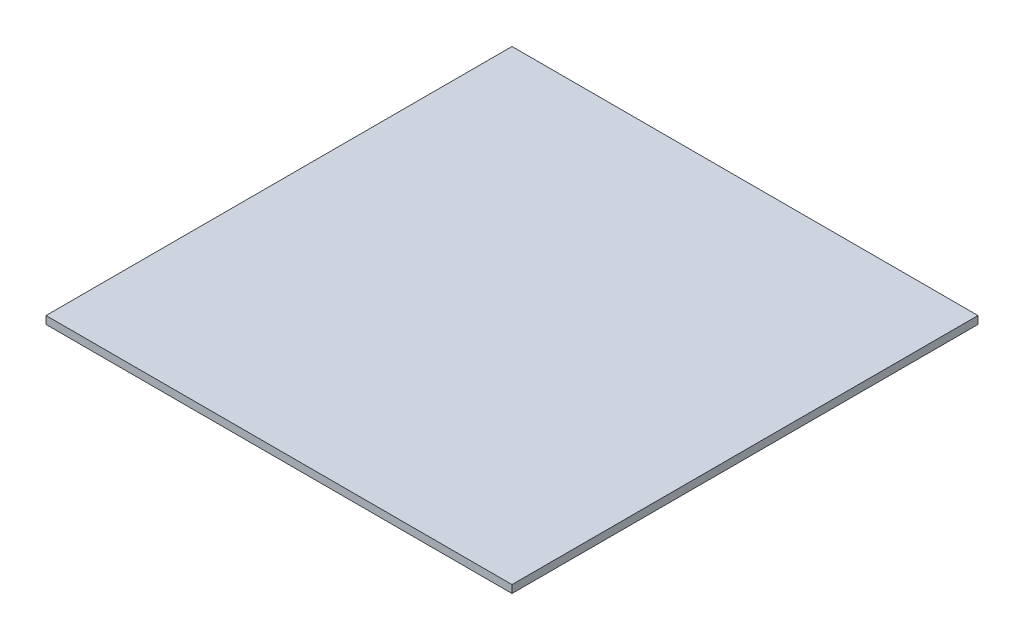
SolidWorks part; units mm, degrees
ref_plane "前基準面" through (0, 0, 0) normal (0, 0, 1) x (1, 0, 0)
ref_plane "上基準面" through (0, 0, 0) normal (0, 1, 0) x (1, 0, 0)
ref_plane "右基準面" through (0, 0, 0) normal (1, 0, 0) x (0, 0, -1)
sketch "草圖1" plane through (0, 0, 0) normal (0, 1, 0) x (1, 0, 0)
  line L0 (135, -150) -> (130, -150) construction
  line L1 (150, 150) -> (-150, 150)
  line L2 (150, 150) -> (150, -150)
  line L3 (150, -150) -> (-150, -150)
  line L4 (-150, 150) -> (-150, -150)
  line L5 (0, -150) -> (0, 150) construction
  line L6 (150, 0) -> (-150, 0) construction
  line L7 (-135, 150) -> (-130, 150) construction
  line L8 (-135, 150) -> (-135, -150) construction
  line L9 (-135, -150) -> (-130, -150) construction
  line L10 (-130, 150) -> (-130, -150) construction
  line L11 (130, 150) -> (130, -150) construction
  line L12 (135, 150) -> (130, 150) construction
  line L13 (135, 150) -> (135, -150) construction
  point P0 (0, 0)
  dimension "D1" = 300
  dimension "D2" = 270
  dimension "D3" = 5
  dimension "D4" = 300
extrude "填料-伸長1" add sketch "草圖1" along normal blind 5
